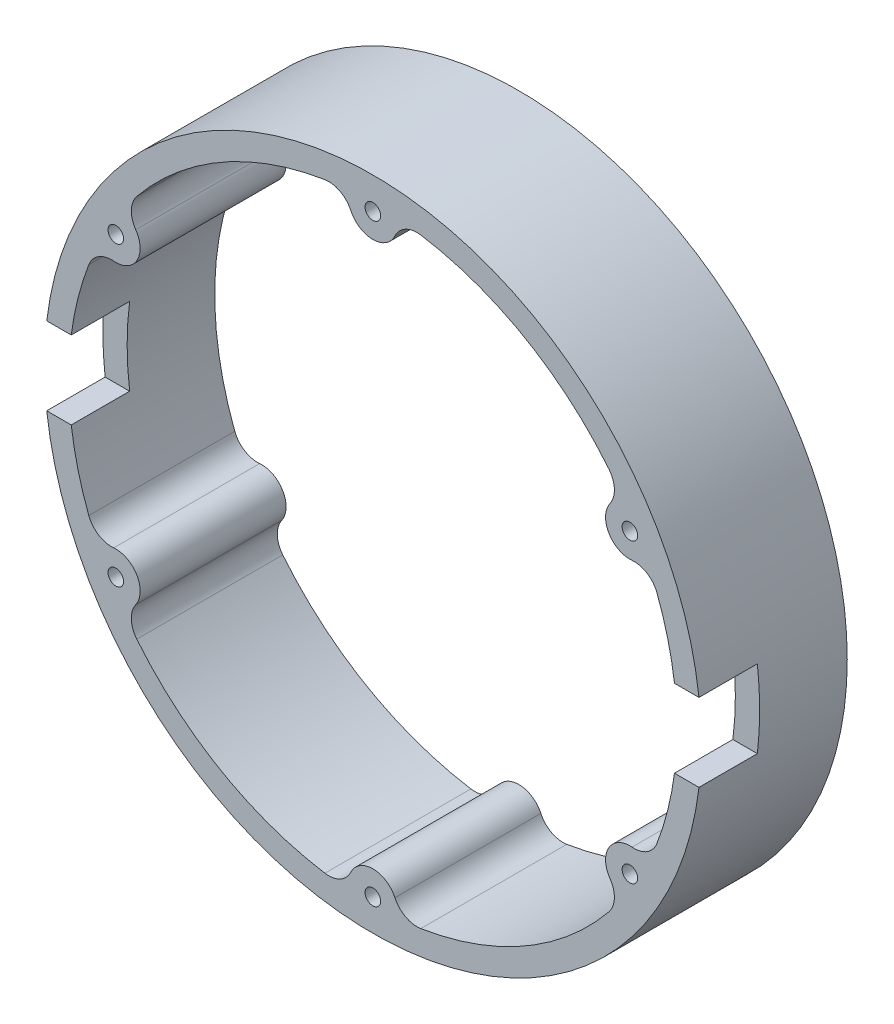
SolidWorks part; units mm, degrees
material "Hêtre"
ref_plane "Plan de face" through (0, 0, 0) normal (0, 0, 1) x (1, 0, 0)
ref_plane "Plan de dessus" through (0, 0, 0) normal (0, 1, 0) x (1, 0, 0)
ref_plane "Plan de droite" through (0, 0, 0) normal (1, 0, 0) x (0, 0, -1)
sketch "Esquisse1" plane through (0, 0, 0) normal (0, 0, 1) x (1, 0, 0)
  circle A0 centre (0, 0) radius 67.5
  dimension "D1" = 135
extrude "Boss.-Extru.1" add sketch "Esquisse1" along normal blind 30
sketch "Esquisse3" plane through (0, 0, 0) normal (0, 0, -1) x (-1, 0, 0)
  circle A0 centre (0, 0) radius 62.5
  dimension "D1" = 125
extrude "Enlèv. mat.-Extru.1" cut sketch "Esquisse3" against normal through all
sketch "Esquisse4" plane through (0, 0, 0) normal (0, 0, -1) x (-1, 0, 0)
  line L0 (0, 0) -> (0, 71.3152) construction
  arc A0 (-9.8547, 61.7182) -> (-4.5332, 58.8904) centre (-9.0663, 56.7807) cw
  circle A1 centre (0, 0) radius 62.5 construction
  arc A2 (-4.5332, 58.8904) -> (0, 56) centre (0, 61) ccw
  arc A3 (-9.8547, 61.7182) -> (9.8547, 61.7182) centre (0, 0) cw
  arc A4 (9.8547, 61.7182) -> (4.5332, 58.8904) centre (9.0663, 56.7807) ccw
  arc A5 (4.5332, 58.8904) -> (0, 56) centre (0, 61) cw
  dimension "D1" = 5
  dimension "D2" = 5
  dimension "D3" = 61
extrude "Boss.-Extru.2" add sketch "Esquisse4" against normal up to surface (30 mm away) up to face at (-62.5, 0, 30)
sketch "Esquisse5" plane through (0, 0, 0) normal (0, 0, -1) x (-1, 0, 0)
  circle A0 centre (0, 61) radius 1.6
  arc A1 (-4.5332, 58.8904) -> (4.5332, 58.8904) centre (0, 61) ccw construction
  dimension "D1" = 3.2
extrude "Enlèv. mat.-Extru.2" cut sketch "Esquisse5" against normal blind 120
pattern_circular "Répétition circulaire1" count 6 over 360 about axis through (0, 0, 0) along (0, 0, 1) of "Enlèv. mat.-Extru.2", "Boss.-Extru.2"
sketch "Esquisse7" plane through (0, 0, 0) normal (1, 0, 0) x (0, 0, -1)
  line L0 (-30, -8) -> (-30, 8)
  line L1 (-30, 8) -> (-18, 8)
  line L2 (-18, 8) -> (-18, -8)
  line L3 (-18, -8) -> (-30, -8)
  line L4 (-30, 22.3247) -> (-30, -22.3247) construction
  line L5 (0, 0) -> (-34.8639, 0) construction
  dimension "D1" = 16
  dimension "D2" = 12
extrude "Enlèv. mat.-Extru.3" cut sketch "Esquisse7" against normal through all both and the other way through all
